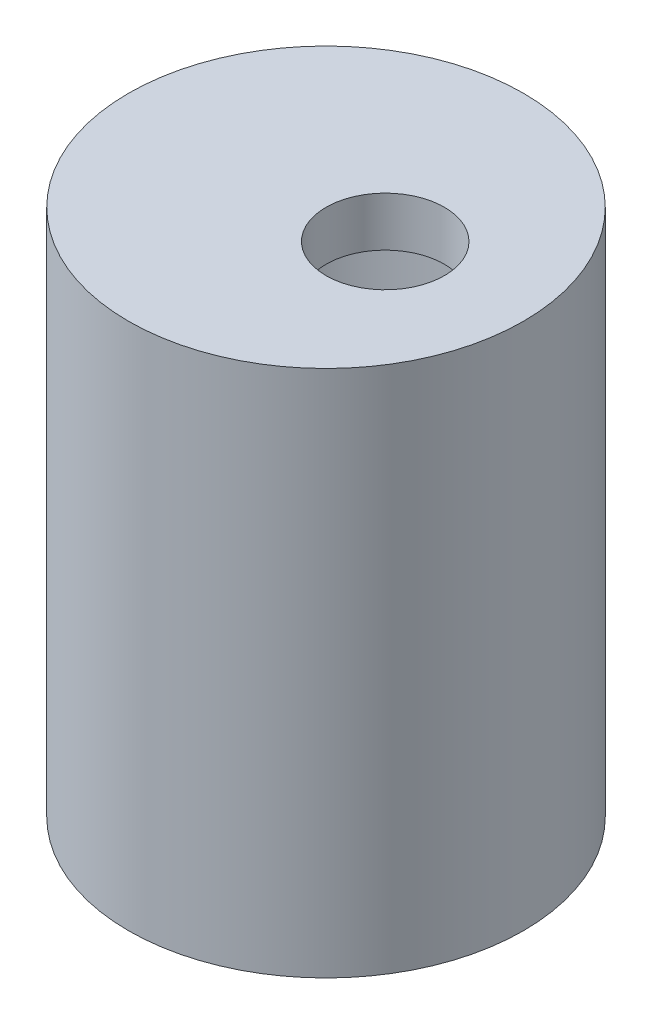
SolidWorks part; units mm, degrees
material "6061-T6 (SS)"
ref_plane "Piano frontale" through (0, 0, 0) normal (0, 0, 1) x (1, 0, 0)
ref_plane "Piano superiore" through (0, 0, 0) normal (0, 1, 0) x (1, 0, 0)
ref_plane "Piano destro" through (0, 0, 0) normal (1, 0, 0) x (0, 0, -1)
sketch "Schizzo1" plane through (0, 0, 0) normal (0, 0, 1) x (1, 0, 0)
  line L0 (0, 0) -> (0, 23.6846) construction
  line L1 (-14, 0) -> (-14, 38)
  line L2 (-14, 38) -> (0, 38)
  line L3 (0, 38) -> (0, 43)
  line L4 (0, 43) -> (-20, 43)
  line L5 (-20, 43) -> (-20, 0)
  line L6 (-20, 0) -> (-14, 0)
  line L7 (-20, 0) -> (-20, -10.4579)
  line L8 (-20, -10.4579) -> (-18, -10.4579)
  line L9 (-18, 0) -> (-18, -12) construction
  line L10 (-18, -10.4579) -> (-18, 0)
  line L11 (-18, 0) -> (-18, -12) construction
  dimension "D1" = 28
  dimension "D2" = 40
  dimension "D3" = 5
  dimension "D4" = 38
revolve "Rivoluzione1" add sketch "Schizzo1" angle 360 about L0 region at (-14.8659, 25.5549, 0) region at (-19, -5.229, 0)
sketch "Schizzo2" plane through (0, 43, 0) normal (0, 1, 0) x (1, 0, 0)
  line L0 (0, 0) -> (6, 0) construction
  circle A0 centre (6, 0) radius 6
  dimension "D1" = 12
  dimension "D2" = 6
extrude "Taglio-Estrusione1" cut sketch "Schizzo2" against normal blind 11
